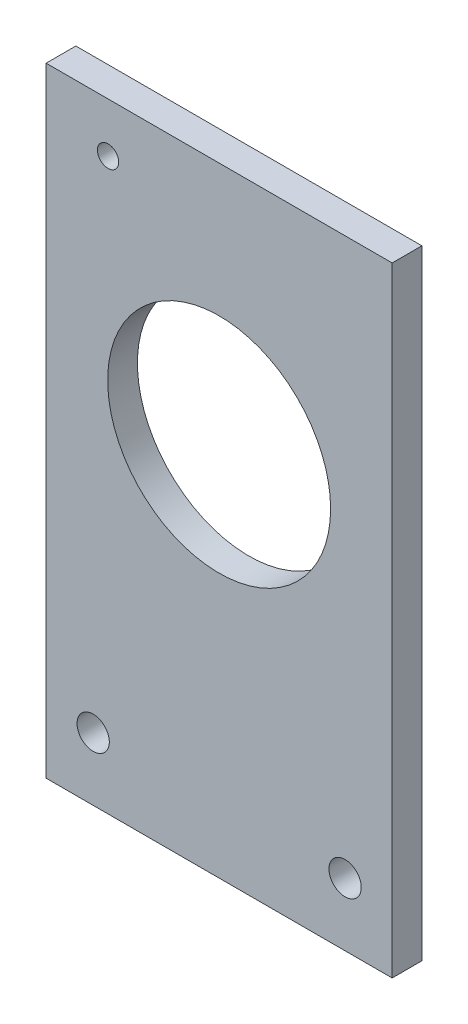
SolidWorks part; units mm, degrees
ref_plane "Front Plane" through (0, 0, 0) normal (0, 0, 1) x (1, 0, 0)
ref_plane "Top Plane" through (0, 0, 0) normal (0, 1, 0) x (1, 0, 0)
ref_plane "Right Plane" through (0, 0, 0) normal (1, 0, 0) x (0, 0, -1)
sketch "Sketch2" plane through (0, 0, 0) normal (0, 0, 1) x (1, 0, 0)
  line L0 (-55, 66.3) -> (55, 66.3) construction
  line L1 (-34.925, 0) -> (34.925, 0)
  line L2 (-34.925, 0) -> (-34.925, 75.8)
  line L3 (-34.925, 75.8) -> (34.925, 75.8) construction
  line L4 (34.925, 0) -> (34.925, 75.8)
  line L5 (0, 66.3) -> (0, 0) construction
  line L6 (0, 66.3) -> (0, 75.8) construction
  line L7 (-34.925, 25.4) -> (34.925, 25.4) construction
  line L10 (34.925, 108.3) -> (-34.925, 108.3) construction
  line L11 (34.925, 75.8) -> (34.925, 108.3)
  line L12 (34.925, 108.3) -> (-34.925, 108.3) construction
  line L13 (-34.925, 108.3) -> (-34.925, 75.8)
  line L14 (34.925, 108.3) -> (34.925, 125)
  line L15 (34.925, 125) -> (-34.925, 125)
  line L16 (-34.925, 108.3) -> (-34.925, 125)
  circle A0 centre (-55, 66.3) radius 3 construction
  circle A1 centre (55, 66.3) radius 3 construction
  circle A2 centre (-55, 66.3) radius 15 construction
  circle A3 centre (55, 66.3) radius 15 construction
  circle A6 centre (0, 75.8) radius 22.5
  circle A7 centre (-55, 66.3) radius 15.6 construction
  point P6 (0, 0)
  dimension "D1" = 6
  dimension "D2" = 30
  dimension "D5" = 45
  dimension "D9" = 125
  dimension "D3" = 110
  dimension "D4" = 9.5
  dimension "D6" = 69.85
  dimension "D7" = 0.6
  dimension "D8" = 32.5
  dimension "D10" = 25.4
  dimension "D11" = 25.3
extrude "Boss-Extrude1" add sketch "Sketch2" along normal mid plane 6
sketch "Sketch3" plane through (0, 0, 3) normal (0, 0, 1) x (1, 0, 0)
  line L0 (34.925, 125) -> (-34.925, 125) construction
  line L1 (-34.925, 0) -> (-25.425, 0) construction
  line L2 (-34.925, 0) -> (-34.925, 12.7) construction
  line L3 (-34.925, 12.7) -> (-25.425, 12.7) construction
  line L4 (-25.425, 0) -> (-25.425, 12.7) construction
  line L5 (34.925, 0) -> (25.425, 0) construction
  line L6 (34.925, 0) -> (34.925, 12.7) construction
  line L7 (34.925, 12.7) -> (25.425, 12.7) construction
  line L8 (25.425, 0) -> (25.425, 12.7) construction
  line L11 (-34.925, 125) -> (-34.925, 0) construction
  circle A0 centre (-25.425, 12.7) radius 3.2576
  circle A1 centre (25.425, 12.7) radius 3.2576
  circle A4 centre (-22.425, 115) radius 2.15
  dimension "D1" = 12.7
  dimension "D2" = 6.5151
  dimension "D7" = 4.3
  dimension "D3" = 9.5
  dimension "D8" = 12.5
  dimension "D9" = 10
extrude "Cut-Extrude1" cut sketch "Sketch3" against normal blind 6
